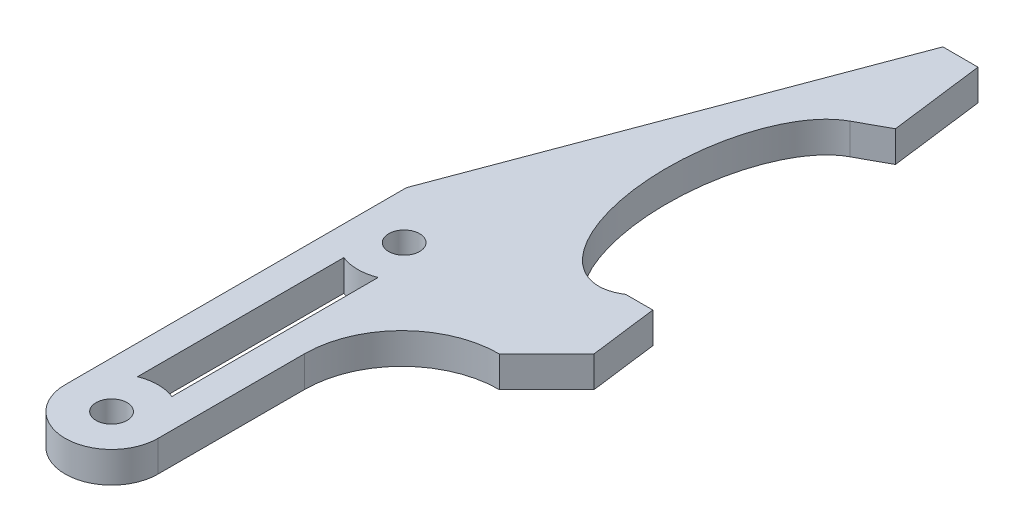
SolidWorks part; units mm, degrees
ref_plane "Alzado" through (0, 0, 0) normal (0, 0, 1) x (1, 0, 0)
ref_plane "Planta" through (0, 0, 0) normal (0, 1, 0) x (1, 0, 0)
ref_plane "Vista lateral" through (0, 0, 0) normal (1, 0, 0) x (0, 0, -1)
sketch "Croquis1" plane through (0, 0, 0) normal (0, 1, 0) x (1, 0, 0)
  line L0 (-12.5, 40) -> (12.5, -40) construction
  line L1 (-12.5, 40) -> (12.5, 40) construction
  line L2 (-12.5, 40) -> (-12.5, -40) construction
  line L3 (-12.5, -40) -> (12.5, -40) construction
  line L4 (12.5, 40) -> (12.5, -40) construction
  line L5 (-12.5, 0) -> (-12.5, -40)
  line L6 (-12.5, -40) -> (-2.975, -40)
  line L7 (-2.975, -40) -> (-2.975, -20)
  line L8 (7.025, -10) -> (12.5, -10)
  line L9 (12.5, -10) -> (12.5, 40)
  line L10 (12.5, 40) -> (2.5, 40)
  line L11 (2.5, 40) -> (-12.5, 0)
  circle A0 centre (-7.7375, -5) radius 1.5875
  circle A1 centre (-7.7375, -35) radius 1.5875
  arc A2 (-2.975, -20) -> (7.025, -10) centre (7.025, -20) cw
  dimension "D5" = 3.175
  dimension "D6" = 3.175
  dimension "D12" = 10
  dimension "D1" = 25
  dimension "D2" = 80
  dimension "D3" = 9.525
  dimension "D4" = 30
  dimension "D7" = 4.7625
  dimension "D8" = 5
  dimension "D9" = 10
  dimension "D10" = 40
  dimension "D11" = 50
extrude "Saliente-Extruir1" add sketch "Croquis1" along normal blind 3.175
sketch "Croquis2" plane through (0, 3.175, 0) normal (0, 1, 0) x (1, 0, 0)
  line L0 (12.5, -10) -> (6.1, 40)
  line L1 (12.5, 40) -> (2.5, 40) construction
  line L2 (6.1, 40) -> (12.5, 40)
  line L3 (12.5, 40) -> (12.5, -10)
  dimension "D1" = 6.4
extrude "Cortar-Extruir1" cut sketch "Croquis2" against normal blind 3.175
sketch "Croquis3" plane through (0, 3.175, 0) normal (0, 1, 0) x (1, 0, 0)
  line L1 (-2.975, -40) -> (-2.975, -20) construction
  line L2 (-12.5, -35) -> (-12.5, -40)
  line L3 (-12.5, -40) -> (-2.975, -40)
  line L4 (-2.975, -40) -> (-2.975, -35)
  line L5 (-9.5, -9.4271) -> (-9.5, -30.5756)
  line L6 (-5.975, -14.8038) -> (-5.975, -30.5756)
  line L7 (-12.5, 0) -> (-12.5, -40) construction
  line L8 (-5.975, -14.8038) -> (-5.975, -9.4271)
  line L22 (7.025, -6) -> (7.9554, -6)
  line L23 (7.9554, -6) -> (3.2646, 30.6468)
  line L24 (3.2646, 30.6468) -> (-8.5, -0.7253)
  line L25 (-8.5, -0.7253) -> (-8.5, -36)
  line L26 (-8.5, -36) -> (-6.975, -36)
  line L27 (-6.975, -36) -> (-6.975, -20)
  line L28 (7.025, -6) -> (7.9554, -6)
  arc A2 (-9.5, -9.4271) -> (-5.975, -9.4271) centre (-7.7375, -5) ccw
  arc A3 (-12.5, -35) -> (-2.975, -35) centre (-7.7375, -35) ccw
  arc A4 (-5.975, -30.5756) -> (-9.5, -30.5756) centre (-7.7375, -35) ccw
  arc A6 (7.025, -6) -> (-6.975, -20) centre (7.025, -20) ccw
  dimension "D1" = 9.53
  dimension "D2" = 3
  dimension "D3" = 3
  dimension "D5" = 4
extrude "Cortar-Extruir3" cut sketch "Croquis3" against normal blind 10 contours A4 L6 L8 A2 L5 | A3 L4 L3 L2 region at (-9.0022, 3.175, 20.0013) region at (-7.5171, 3.175, 18.7603) region at (-6.4486, 3.175, 23.4107)
sketch "Croquis5" plane through (0, 3.175, 0) normal (0, 1, 0) x (1, 0, 0)
  line L0 (6.1, 40) -> (12.5, -10) construction
  line L1 (7.025, -10) -> (11.8787, -5.1463)
  line L2 (11.8787, -5.1463) -> (12.5, -10)
  line L3 (12.5, -10) -> (7.025, -10)
  circle A0 centre (9.3, 15) radius 10
  dimension "D1" = 20
  dimension "D2" = 25
  dimension "D3" = 45
extrude "Cortar-Extruir8" cut sketch "Croquis5" against normal blind 10
fillet "Redondeo2" radius 2 2 edges at (10.5696, 1.5875, -5.0809) (8.0304, 1.5875, -24.9191)
sketch "Esquisse1" plane through (0, 3.175, 0) normal (0, 1, 0) x (1, 0, 0)
  ellipse E0 centre (6.0963, 15.0993) end of major axis (6.0963, 1.0993) minor radius 7
  dimension "D1" = 14
  dimension "D2" = 7
extrude "Enlèv. mat.-Extru.1" cut sketch "Esquisse1" against normal through all
sketch "Esquisse2" plane through (0, 3.175, 0) normal (0, 1, 0) x (1, 0, 0)
  line L6 (8.077, 5.0615) -> (14.8896, 5.0615)
  line L7 (8.077, 5.0615) -> (8.077, 1.7615)
  line L8 (8.077, 1.7615) -> (14.8896, 1.7615)
  line L9 (14.8896, 5.0615) -> (14.8896, 1.7615)
  dimension "D1" = 6.8126
  dimension "D2" = 3.3
extrude "Enlèv. mat.-Extru.2" cut sketch "Esquisse2" against normal through all
chamfer "Chanfrein1" distance 5 angle 45 1 edges at (7.5335, 1.5875, -28.801) first distance on face at (3.492, 1.5875, -14.8333)
